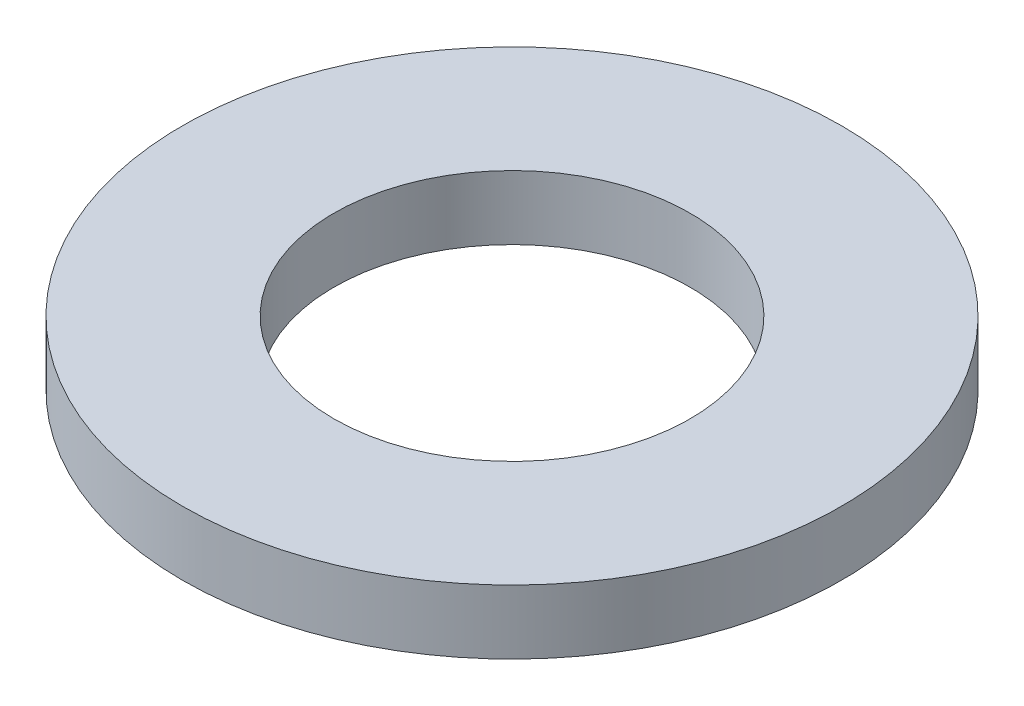
SolidWorks part; units mm, degrees
ref_plane "Front Plane" through (0, 0, 0) normal (0, 0, 1) x (1, 0, 0)
ref_plane "Top Plane" through (0, 0, 0) normal (0, 1, 0) x (1, 0, 0)
ref_plane "Right Plane" through (0, 0, 0) normal (1, 0, 0) x (0, 0, -1)
sketch "Sketch1" plane through (0, 0, 0) normal (0, 1, 0) x (1, 0, 0)
  circle A0 centre (0, 0) radius 92.5
  dimension "FLANGE_OD" = 185
extrude "Boss-Extrude1" add sketch "Sketch1" along normal blind 18
sketch "Sketch2" plane through (0, 0, 0) normal (0, 1, 0) x (1, 0, 0)
  circle A0 centre (0, 0) radius 50
  dimension "BORE_D" = 100
extrude "Cut-Extrude1" cut sketch "Sketch2" along normal through all
sketch "Sketch3" plane through (0, 18, 0) normal (0, 1, 0) x (1, 0, 0)
  circle A0 centre (0, 0) radius 37.5312 construction
  circle A1 centre (-37.5312, 0) radius 7.6138
  dimension "BOLT_D" = 15.2275
  dimension "BOLT_PCD" = 75.0624
extrude "Cut-Extrude2" cut sketch "Sketch3" against normal blind 11.5905 rebuild error yes
pattern_circular "CirPattern1" count 3 over 360 rebuild error yes
